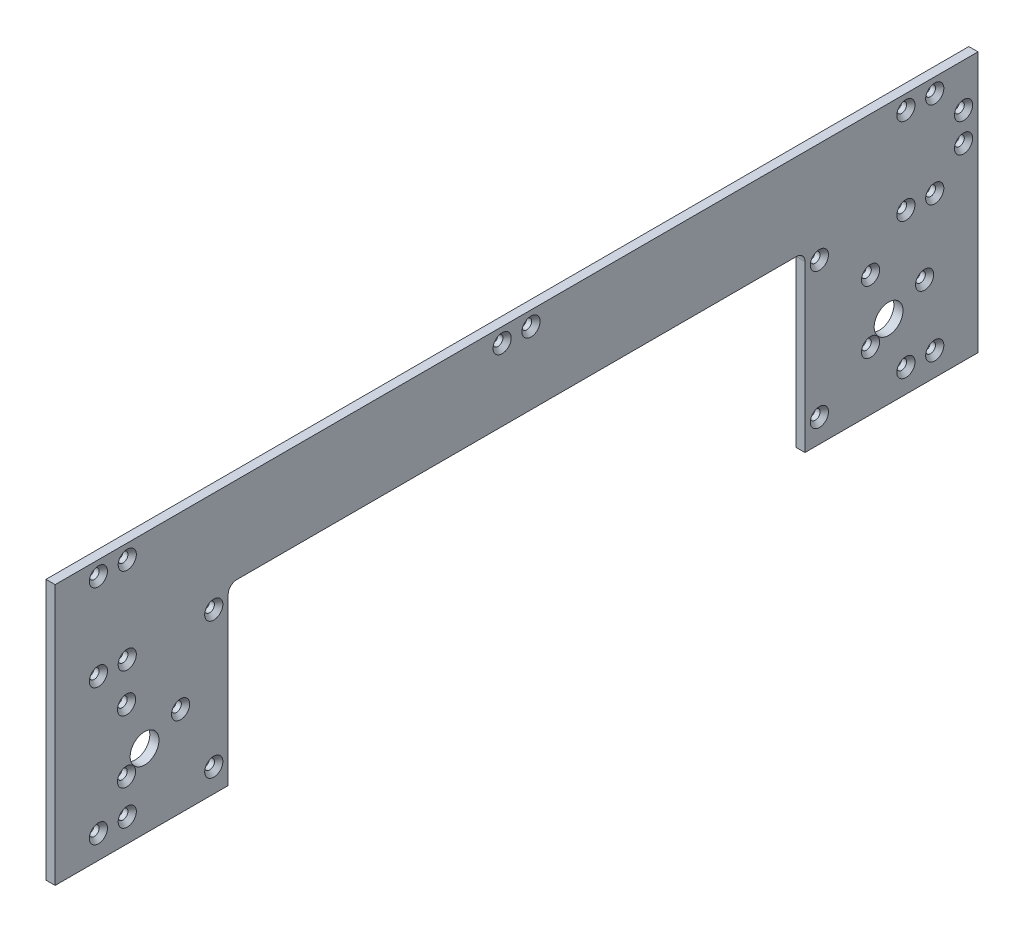
SolidWorks part; units mm, degrees
material "Garolite (G-10/FR4)"
ref_plane "Front Plane" through (0, 0, 0) normal (0, 0, 1) x (1, 0, 0)
ref_plane "Top Plane" through (0, 0, 0) normal (0, 1, 0) x (1, 0, 0)
ref_plane "Right Plane" through (0, 0, 0) normal (1, 0, 0) x (0, 0, -1)
sketch "Sketch1" plane through (0, 0, 0) normal (1, 0, 0) x (0, 0, -1)
  line L0 (160, 0) -> (160, 3.175)
  line L1 (-160, 0) -> (160, 0)
  line L2 (160, 3.175) -> (160, 47.175)
  line L3 (-160, 90.35) -> (160, 90.35)
  line L4 (-160, 3.175) -> (-160, 47.175)
  line L5 (-160, 3.175) -> (-160, 0)
  line L6 (160, 47.175) -> (160, 50.35)
  line L7 (160, 50.35) -> (160, 60.35)
  line L8 (160, 60.35) -> (160, 90.35)
  line L9 (-160, 47.175) -> (-160, 50.35)
  line L10 (-160, 50.35) -> (-160, 60.35)
  line L11 (-160, 60.35) -> (-160, 90.35)
  dimension "D1" = 320
  dimension "D2" = 30
  dimension "D3" = 3.175
  dimension "D4" = 44
  dimension "D5" = 3.175
  dimension "D6" = 10
extrude "Boss-Extrude1" add sketch "Sketch1" along normal blind 3.175
hole_wizard "CSK for M3 Flat Head Machine Screw1" positions "Sketch3" profile "Sketch2" countersink size "M3" standard "Ansi Metric" end condition through all
sketch "Sketch3" plane through (3.175, 0, 0) normal (1, 0, 0) x (0, 0, -1)
  line L0 (-105, 8.175) -> (-160, 8.175) construction
  line L1 (-160, 90.35) -> (-160, 0) construction
  line L3 (-160, 0) -> (160, 0) construction
  line L4 (-105, 55.35) -> (-160, 55.35) construction
  line L10 (-145, 8.175) -> (-145, 85.35) construction
  line L12 (-135, 8.175) -> (-135, 85.35) construction
  line L14 (-105, 8.175) -> (-105, 85.35) construction
  line L16 (-105, 85.35) -> (-160, 85.35) construction
  line L17 (-105, 85.35) -> (-5, 85.35) construction
  point P0 (-145, 8.175)
  point P1 (-135, 8.175)
  point P3 (-105, 8.175)
  point P15 (-145, 55.35)
  point P17 (-135, 55.35)
  point P19 (-105, 55.35)
  point P55 (-145, 85.35)
  point P57 (-135, 85.35)
  point P59 (-5, 85.35)
  dimension "D1" = 8.175
  dimension "D2" = 15
  dimension "D3" = 10
  dimension "D4" = 30
  dimension "D5" = 30
  dimension "D6" = 140
  dimension "D8" = 55.35
sketch "Sketch2" plane through (3.175, 8.175, 145) normal (0, 1, 0) x (0, 0, -1)
  line L0 (0, 0) -> (0, 3.175)
  line L1 (0, 3.175) -> (1.7, 3.175)
  line L2 (1.7, 3.175) -> (1.7, 1.45)
  line L3 (1.7, 1.45) -> (3.15, 0)
  line L5 (3.15, 0) -> (0, 0)
  line L6 (-1.7, 1.45) -> (-3.15, 0) construction
  line L11 (0, -6.35) -> (0, 107.95) construction
  dimension "Thru Hole Dia." = 3.4
  dimension "Thru Hole Depth" = 3.175
  dimension "Near C'Sink Dia." = 6.3
  dimension "Near C'Sink Angle" = 90
mirror "Mirror1" about plane through (0, 0, 0) normal (0, 0, 1) of "CSK for M3 Flat Head Machine Screw1"
sketch "Sketch4" plane through (3.175, 0, 0) normal (1, 0, 0) x (0, 0, -1)
  line L0 (-100, 57.35) -> (-100, 0)
  line L1 (-160, 0) -> (160, 0) construction
  line L2 (-160, 90.35) -> (-160, 0) construction
  line L3 (-97, 60.35) -> (97, 60.35)
  line L4 (0, 60.35) -> (0, 0) construction
  line L5 (100, 0) -> (-100, 0)
  line L6 (100, 57.35) -> (100, 0)
  line L7 (-129, 25.675) -> (129, 25.675) construction
  line L8 (160, 0) -> (160, 90.35) construction
  arc A0 (-100, 57.35) -> (-97, 60.35) centre (-97, 57.35) cw
  arc A1 (100, 57.35) -> (97, 60.35) centre (97, 57.35) ccw
  circle A2 centre (-129, 25.675) radius 5
  circle A3 centre (129, 25.675) radius 5
  dimension "D3" = 3
  dimension "D4" = 10
  dimension "D1" = 60
  dimension "D2" = 60.35
  dimension "D5" = 31
  dimension "D6" = 25.675
  dimension "D7" = 31
extrude "Cut-Extrude1" cut sketch "Sketch4" against normal through all
hole_wizard "CSK for M3 Flat Head Machine Screw2" positions "Sketch6" profile "Sketch5" countersink size "M3" standard "Ansi Metric" end condition through all
sketch "Sketch6" plane through (3.175, 0, 0) normal (1, 0, 0) x (0, 0, -1)
  line L0 (155, 65.35) -> (155, 90.35) construction
  line L1 (160, 90.35) -> (-160, 90.35) construction
  line L4 (160, 0) -> (160, 90.35) construction
  point P0 (155, 65.35)
  point P1 (155, 75.35)
  dimension "D1" = 10
  dimension "D2" = 5
  dimension "D3" = 15
sketch "Sketch5" plane through (3.175, 65.35, -155) normal (0, 1, 0) x (0, 0, -1)
  line L0 (0, 0) -> (0, 3.175)
  line L1 (0, 3.175) -> (1.7, 3.175)
  line L2 (1.7, 3.175) -> (1.7, 1.45)
  line L3 (1.7, 1.45) -> (3.15, 0)
  line L5 (3.15, 0) -> (0, 0)
  line L6 (-1.7, 1.45) -> (-3.15, 0) construction
  line L11 (0, -6.35) -> (0, 107.95) construction
  dimension "Thru Hole Dia." = 3.4
  dimension "Thru Hole Depth" = 3.175
  dimension "Near C'Sink Dia." = 6.3
  dimension "Near C'Sink Angle" = 90
hole_wizard "CSK for M3 Flat Head Machine Screw3" positions "Sketch8" profile "Sketch7" countersink size "M3" standard "Ansi Metric" end condition through all
sketch "Sketch8" plane through (3.175, 0, 0) normal (1, 0, 0) x (0, 0, -1)
  line L0 (-116.5, 31.175) -> (-129, 31.175) construction
  line L2 (-135.25, 20.3497) -> (-129, 31.175) construction
  line L3 (-129, 31.175) -> (-135.25, 42.0003) construction
  line L4 (-129, 31.175) -> (-129, 25.675) construction
  line L6 (-160, 0) -> (-100, 0) construction
  circle A0 centre (-129, 31.175) radius 12.5
  point P1 (-116.5, 31.175)
  point P26 (-135.25, 20.3497)
  point P28 (-135.25, 42.0003)
  dimension "D1" = 25
  dimension "D2" = 120
  dimension "D3" = 120
  dimension "D4" = 31.175
sketch "Sketch7" plane through (3.175, 31.175, 116.5) normal (0, 1, 0) x (0, 0, -1)
  line L0 (0, 0) -> (0, 3.175)
  line L1 (0, 3.175) -> (1.7, 3.175)
  line L2 (1.7, 3.175) -> (1.7, 1.45)
  line L3 (1.7, 1.45) -> (3.15, 0)
  line L5 (3.15, 0) -> (0, 0)
  line L6 (-1.7, 1.45) -> (-3.15, 0) construction
  line L11 (0, -6.35) -> (0, 107.95) construction
  dimension "Thru Hole Dia." = 3.4
  dimension "Thru Hole Depth" = 3.175
  dimension "Near C'Sink Dia." = 6.3
  dimension "Near C'Sink Angle" = 90
pattern_linear "LPattern1" count 2 spacing 258 along (0, 0, -1) of "CSK for M3 Flat Head Machine Screw3"
